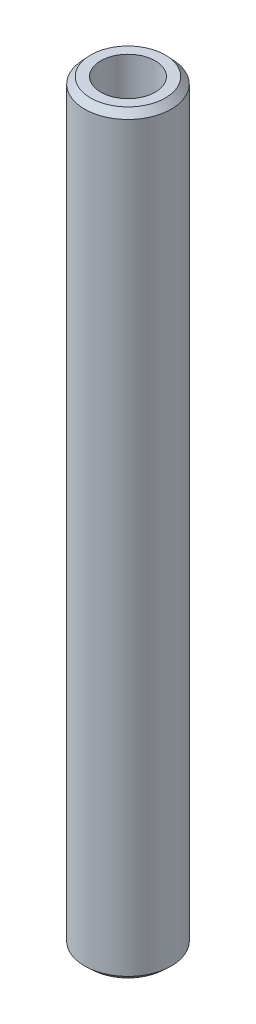
SolidWorks part; units mm, degrees
ref_plane "Front Plane" through (0, 0, 0) normal (0, 0, 1) x (1, 0, 0)
ref_plane "Top Plane" through (0, 0, 0) normal (0, 1, 0) x (1, 0, 0)
ref_plane "Right Plane" through (0, 0, 0) normal (1, 0, 0) x (0, 0, -1)
sketch "Sketch1" plane through (0, 0, 0) normal (0, 1, 0) x (1, 0, 0)
  circle A0 centre (0, 0) radius 7.5
  dimension "SHAFT_OD" = 15
extrude "Boss-Extrude1" add sketch "Sketch1" along normal blind 130.4959
sketch "Sketch2" plane through (0, 0, 0) normal (0, 1, 0) x (1, 0, 0)
  circle A0 centre (0, 0) radius 4.7079
  dimension "BORE_D" = 9.4157
extrude "Cut-Extrude1" cut sketch "Sketch2" along normal through all
chamfer "Chamfer1" distance 1.1421 angle 42.525 2 edges at (0, 130.4959, 7.5) (0, 0, 7.5) first distance on face at (0, 130.4959, 7.5) first distance on face at (0, 0, 4.7079)
